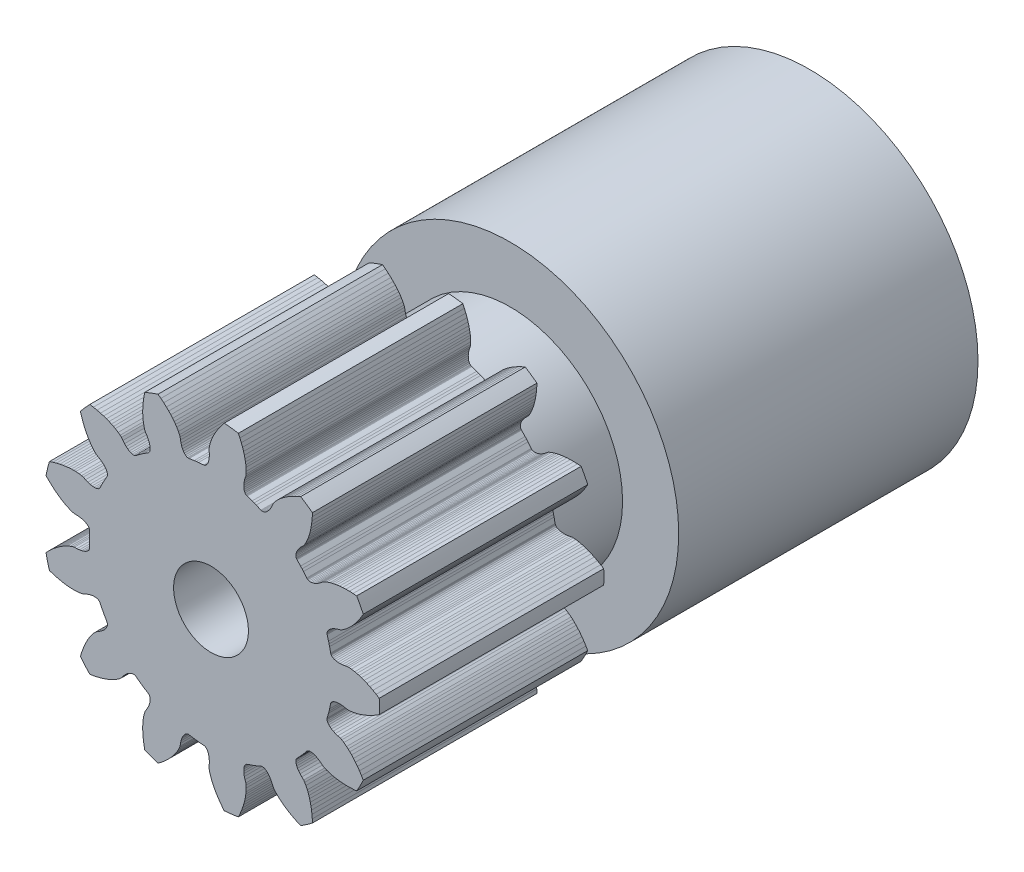
SolidWorks part; units mm, degrees
ref_plane "Front Plane" through (0, 0, 0) normal (0, 0, 1) x (1, 0, 0)
ref_plane "Top Plane" through (0, 0, 0) normal (0, 1, 0) x (1, 0, 0)
ref_plane "Right Plane" through (0, 0, 0) normal (1, 0, 0) x (0, 0, -1)
sketch "Model" plane through (0, 0, 0) normal (0, 0, 1) x (1, 0, 0)
  line L0 (4.021, 1.8382) -> (3.9675, 1.7546)
  line L1 (3.9675, 1.7546) -> (3.9132, 1.6769)
  line L2 (3.9132, 1.6769) -> (3.8601, 1.6075)
  line L3 (3.8601, 1.6075) -> (3.8089, 1.546)
  line L4 (3.8089, 1.546) -> (3.7579, 1.4897)
  line L5 (3.7579, 1.4897) -> (3.7105, 1.4416)
  line L6 (3.7105, 1.4416) -> (3.6651, 1.3992)
  line L7 (3.6651, 1.3992) -> (3.6228, 1.3629)
  line L8 (3.6228, 1.3629) -> (3.5504, 1.3082)
  line L9 (3.5504, 1.3082) -> (3.4948, 1.2729)
  line L10 (3.4948, 1.2729) -> (3.4534, 1.2516)
  line L11 (3.4534, 1.2516) -> (3.3881, 1.2342)
  line L12 (3.3881, 1.2342) -> (3.3241, 1.2119)
  line L13 (3.3241, 1.2119) -> (3.2681, 1.1867)
  line L14 (3.2681, 1.1867) -> (3.2199, 1.1592)
  line L15 (3.2199, 1.1592) -> (3.1798, 1.13)
  line L16 (3.1798, 1.13) -> (3.1477, 1.0998)
  line L17 (3.1477, 1.0998) -> (3.1237, 1.0692)
  line L18 (3.1237, 1.0692) -> (3.1078, 1.0388)
  line L19 (3.1078, 1.0388) -> (3.0998, 1.0092)
  line L20 (3.0998, 1.0092) -> (3.0988, 0.9949)
  line L21 (3.0988, 0.9949) -> (3.0997, 0.9811)
  line L22 (3.0997, 0.9811) -> (3.1026, 0.9677)
  line L23 (3.1026, 0.9677) -> (3.1411, 0.8342)
  line L24 (3.1411, 0.8342) -> (3.1556, 0.7778)
  line L25 (3.1556, 0.7778) -> (3.169, 0.7211)
  line L26 (3.169, 0.7211) -> (3.1969, 0.585)
  line L27 (3.1969, 0.585) -> (3.2006, 0.5718)
  line L28 (3.2006, 0.5718) -> (3.2062, 0.5591)
  line L29 (3.2062, 0.5591) -> (3.2138, 0.5469)
  line L30 (3.2138, 0.5469) -> (3.2346, 0.5244)
  line L31 (3.2346, 0.5244) -> (3.2628, 0.5049)
  line L32 (3.2628, 0.5049) -> (3.2983, 0.489)
  line L33 (3.2983, 0.489) -> (3.3407, 0.4771)
  line L34 (3.3407, 0.4771) -> (3.3898, 0.4699)
  line L35 (3.3898, 0.4699) -> (3.4452, 0.468)
  line L36 (3.4452, 0.468) -> (3.5066, 0.4717)
  line L37 (3.5066, 0.4717) -> (3.5735, 0.4817)
  line L38 (3.5735, 0.4817) -> (3.6395, 0.4967)
  line L39 (3.6395, 0.4967) -> (3.686, 0.497)
  line L40 (3.686, 0.497) -> (3.7517, 0.4916)
  line L41 (3.7517, 0.4916) -> (3.8412, 0.4768)
  line L42 (3.8412, 0.4768) -> (3.8955, 0.4643)
  line L43 (3.8955, 0.4643) -> (3.9555, 0.4479)
  line L44 (3.9555, 0.4479) -> (4.0198, 0.4273)
  line L45 (4.0198, 0.4273) -> (4.0911, 0.4012)
  line L46 (4.0911, 0.4012) -> (4.165, 0.3705)
  line L47 (4.165, 0.3705) -> (4.2442, 0.3337)
  line L48 (4.2442, 0.3337) -> (4.3284, 0.2902)
  line L49 (4.3284, 0.2902) -> (4.4146, 0.241)
  line L50 (4.4146, 0.241) -> (4.496, 0.1901)
  line L51 (4.496, -0.1901) -> (4.4146, -0.241)
  line L52 (4.4146, -0.241) -> (4.3284, -0.2902)
  line L53 (4.3284, -0.2902) -> (4.2442, -0.3337)
  line L54 (4.2442, -0.3337) -> (4.165, -0.3705)
  line L55 (4.165, -0.3705) -> (4.0911, -0.4012)
  line L56 (4.0911, -0.4012) -> (4.0198, -0.4273)
  line L57 (4.0198, -0.4273) -> (3.9555, -0.4479)
  line L58 (3.9555, -0.4479) -> (3.8955, -0.4643)
  line L59 (3.8955, -0.4643) -> (3.8412, -0.4768)
  line L60 (3.8412, -0.4768) -> (3.7517, -0.4916)
  line L61 (3.7517, -0.4916) -> (3.686, -0.497)
  line L62 (3.686, -0.497) -> (3.6395, -0.4967)
  line L63 (3.6395, -0.4967) -> (3.5735, -0.4817)
  line L64 (3.5735, -0.4817) -> (3.5066, -0.4717)
  line L65 (3.5066, -0.4717) -> (3.4452, -0.468)
  line L66 (3.4452, -0.468) -> (3.3898, -0.4699)
  line L67 (3.3898, -0.4699) -> (3.3407, -0.4771)
  line L68 (3.3407, -0.4771) -> (3.2983, -0.489)
  line L69 (3.2983, -0.489) -> (3.2628, -0.5049)
  line L70 (3.2628, -0.5049) -> (3.2346, -0.5244)
  line L71 (3.2346, -0.5244) -> (3.2138, -0.5469)
  line L72 (3.2138, -0.5469) -> (3.2062, -0.5591)
  line L73 (3.2062, -0.5591) -> (3.2006, -0.5718)
  line L74 (3.2006, -0.5718) -> (3.1969, -0.585)
  line L75 (3.1969, -0.585) -> (3.169, -0.7211)
  line L76 (3.169, -0.7211) -> (3.1556, -0.7778)
  line L77 (3.1556, -0.7778) -> (3.1411, -0.8342)
  line L78 (3.1411, -0.8342) -> (3.1026, -0.9677)
  line L79 (3.1026, -0.9677) -> (3.0997, -0.9811)
  line L80 (3.0997, -0.9811) -> (3.0988, -0.9949)
  line L81 (3.0988, -0.9949) -> (3.0998, -1.0092)
  line L82 (3.0998, -1.0092) -> (3.1078, -1.0388)
  line L83 (3.1078, -1.0388) -> (3.1237, -1.0692)
  line L84 (3.1237, -1.0692) -> (3.1477, -1.0998)
  line L85 (3.1477, -1.0998) -> (3.1798, -1.13)
  line L86 (3.1798, -1.13) -> (3.2199, -1.1592)
  line L87 (3.2199, -1.1592) -> (3.2681, -1.1867)
  line L88 (3.2681, -1.1867) -> (3.3241, -1.2119)
  line L89 (3.3241, -1.2119) -> (3.3881, -1.2342)
  line L90 (3.3881, -1.2342) -> (3.4534, -1.2516)
  line L91 (3.4534, -1.2516) -> (3.4948, -1.2729)
  line L92 (3.4948, -1.2729) -> (3.5504, -1.3082)
  line L93 (3.5504, -1.3082) -> (3.6228, -1.3629)
  line L94 (3.6228, -1.3629) -> (3.6651, -1.3992)
  line L95 (3.6651, -1.3992) -> (3.7105, -1.4416)
  line L96 (3.7105, -1.4416) -> (3.7579, -1.4897)
  line L97 (3.7579, -1.4897) -> (3.8089, -1.546)
  line L98 (3.8089, -1.546) -> (3.8601, -1.6075)
  line L99 (3.8601, -1.6075) -> (3.9132, -1.6769)
  line L100 (3.9132, -1.6769) -> (3.9675, -1.7546)
  line L101 (3.9675, -1.7546) -> (4.021, -1.8382)
  line L102 (4.021, -1.8382) -> (4.0693, -1.921)
  line L103 (3.8926, -2.2577) -> (3.7969, -2.265)
  line L104 (3.7969, -2.265) -> (3.6978, -2.2685)
  line L105 (3.6978, -2.2685) -> (3.603, -2.2679)
  line L106 (3.603, -2.2679) -> (3.5158, -2.2636)
  line L107 (3.5158, -2.2636) -> (3.4361, -2.2564)
  line L108 (3.4361, -2.2564) -> (3.3608, -2.2464)
  line L109 (3.3608, -2.2464) -> (3.2943, -2.2348)
  line L110 (3.2943, -2.2348) -> (3.2335, -2.2214)
  line L111 (3.2335, -2.2214) -> (3.1796, -2.2072)
  line L112 (3.1796, -2.2072) -> (3.0935, -2.1788)
  line L113 (3.0935, -2.1788) -> (3.0328, -2.1531)
  line L114 (3.0328, -2.1531) -> (2.9918, -2.1311)
  line L115 (2.9918, -2.1311) -> (2.9404, -2.0872)
  line L116 (2.9404, -2.0872) -> (2.8857, -2.0473)
  line L117 (2.8857, -2.0473) -> (2.8331, -2.0154)
  line L118 (2.8331, -2.0154) -> (2.7831, -1.9914)
  line L119 (2.7831, -1.9914) -> (2.7363, -1.975)
  line L120 (2.7363, -1.975) -> (2.6933, -1.9657)
  line L121 (2.6933, -1.9657) -> (2.6544, -1.9634)
  line L122 (2.6544, -1.9634) -> (2.6204, -1.9676)
  line L123 (2.6204, -1.9676) -> (2.5915, -1.9778)
  line L124 (2.5915, -1.9778) -> (2.5791, -1.9851)
  line L125 (2.5791, -1.9851) -> (2.5683, -1.9937)
  line L126 (2.5683, -1.9937) -> (2.5589, -2.0037)
  line L127 (2.5589, -2.0037) -> (2.4709, -2.1112)
  line L128 (2.4709, -2.1112) -> (2.4327, -2.1551)
  line L129 (2.4327, -2.1551) -> (2.3937, -2.1984)
  line L130 (2.3937, -2.1984) -> (2.2975, -2.2987)
  line L131 (2.2975, -2.2987) -> (2.2888, -2.3092)
  line L132 (2.2888, -2.3092) -> (2.2815, -2.3211)
  line L133 (2.2815, -2.3211) -> (2.2758, -2.3342)
  line L134 (2.2758, -2.3342) -> (2.2691, -2.3641)
  line L135 (2.2691, -2.3641) -> (2.269, -2.3984)
  line L136 (2.269, -2.3984) -> (2.276, -2.4367)
  line L137 (2.276, -2.4367) -> (2.2904, -2.4783)
  line L138 (2.2904, -2.4783) -> (2.3124, -2.5228)
  line L139 (2.3124, -2.5228) -> (2.3422, -2.5695)
  line L140 (2.3422, -2.5695) -> (2.3802, -2.6179)
  line L141 (2.3802, -2.6179) -> (2.4264, -2.6673)
  line L142 (2.4264, -2.6673) -> (2.4762, -2.7131)
  line L143 (2.4762, -2.7131) -> (2.5029, -2.7512)
  line L144 (2.5029, -2.7512) -> (2.5358, -2.8083)
  line L145 (2.5358, -2.8083) -> (2.5744, -2.8904)
  line L146 (2.5744, -2.8904) -> (2.595, -2.9422)
  line L147 (2.595, -2.9422) -> (2.6155, -3.0009)
  line L148 (2.6155, -3.0009) -> (2.6352, -3.0655)
  line L149 (2.6352, -3.0655) -> (2.6542, -3.139)
  line L150 (2.6542, -3.139) -> (2.6709, -3.2173)
  line L151 (2.6709, -3.2173) -> (2.6856, -3.3034)
  line L152 (2.6856, -3.3034) -> (2.6977, -3.3974)
  line L153 (2.6977, -3.3974) -> (2.7061, -3.4962)
  line L154 (2.7061, -3.4962) -> (2.7105, -3.5921)
  line L155 (2.3975, -3.8081) -> (2.3094, -3.7701)
  line L156 (2.3094, -3.7701) -> (2.22, -3.7271)
  line L157 (2.22, -3.7271) -> (2.1364, -3.6825)
  line L158 (2.1364, -3.6825) -> (2.0611, -3.6382)
  line L159 (2.0611, -3.6382) -> (1.9939, -3.5948)
  line L160 (1.9939, -3.5948) -> (1.9318, -3.5509)
  line L161 (1.9318, -3.5509) -> (1.8784, -3.5097)
  line L162 (1.8784, -3.5097) -> (1.8308, -3.4697)
  line L163 (1.8308, -3.4697) -> (1.7897, -3.4321)
  line L164 (1.7897, -3.4321) -> (1.7266, -3.3668)
  line L165 (1.7266, -3.3668) -> (1.6848, -3.3159)
  line L166 (1.6848, -3.3159) -> (1.6587, -3.2774)
  line L167 (1.6587, -3.2774) -> (1.6336, -3.2146)
  line L168 (1.6336, -3.2146) -> (1.6037, -3.1538)
  line L169 (1.6037, -3.1538) -> (1.572, -3.1012)
  line L170 (1.572, -3.1012) -> (1.5389, -3.0567)
  line L171 (1.5389, -3.0567) -> (1.5051, -3.0204)
  line L172 (1.5051, -3.0204) -> (1.4712, -2.9922)
  line L173 (1.4712, -2.9922) -> (1.4379, -2.9721)
  line L174 (1.4379, -2.9721) -> (1.4058, -2.9599)
  line L175 (1.4058, -2.9599) -> (1.3755, -2.9556)
  line L176 (1.3755, -2.9556) -> (1.3612, -2.9563)
  line L177 (1.3612, -2.9563) -> (1.3476, -2.9589)
  line L178 (1.3476, -2.9589) -> (1.3346, -2.9633)
  line L179 (1.3346, -2.9633) -> (1.2067, -3.0177)
  line L180 (1.2067, -3.0177) -> (1.1525, -3.0388)
  line L181 (1.1525, -3.0388) -> (1.0978, -3.059)
  line L182 (1.0978, -3.059) -> (0.9661, -3.1031)
  line L183 (0.9661, -3.1031) -> (0.9534, -3.1084)
  line L184 (0.9534, -3.1084) -> (0.9415, -3.1155)
  line L185 (0.9415, -3.1155) -> (0.9303, -3.1244)
  line L186 (0.9303, -3.1244) -> (0.9105, -3.1478)
  line L187 (0.9105, -3.1478) -> (0.8945, -3.1782)
  line L188 (0.8945, -3.1782) -> (0.883, -3.2153)
  line L189 (0.883, -3.2153) -> (0.8763, -3.2588)
  line L190 (0.8763, -3.2588) -> (0.8751, -3.3084)
  line L191 (0.8751, -3.3084) -> (0.8798, -3.3637)
  line L192 (0.8798, -3.3637) -> (0.891, -3.4242)
  line L193 (0.891, -3.4242) -> (0.9089, -3.4894)
  line L194 (0.9089, -3.4894) -> (0.9317, -3.5531)
  line L195 (0.9317, -3.5531) -> (0.9377, -3.5992)
  line L196 (0.9377, -3.5992) -> (0.9403, -3.665)
  line L197 (0.9403, -3.665) -> (0.9363, -3.7557)
  line L198 (0.9363, -3.7557) -> (0.9305, -3.8111)
  line L199 (0.9305, -3.8111) -> (0.9214, -3.8727)
  line L200 (0.9214, -3.8727) -> (0.9087, -3.939)
  line L201 (0.9087, -3.939) -> (0.8914, -4.0129)
  line L202 (0.8914, -4.0129) -> (0.8698, -4.09)
  line L203 (0.8698, -4.09) -> (0.8429, -4.1731)
  line L204 (0.8429, -4.1731) -> (0.8098, -4.2619)
  line L205 (0.8098, -4.2619) -> (0.7714, -4.3534)
  line L206 (0.7714, -4.3534) -> (0.7307, -4.4403)
  line L207 (0.3532, -4.4861) -> (0.2929, -4.4115)
  line L208 (0.2929, -4.4115) -> (0.2336, -4.3319)
  line L209 (0.2336, -4.3319) -> (0.1803, -4.2535)
  line L210 (0.1803, -4.2535) -> (0.1342, -4.1793)
  line L211 (0.1342, -4.1793) -> (0.0949, -4.1096)
  line L212 (0.0949, -4.1096) -> (0.0603, -4.042)
  line L213 (0.0603, -4.042) -> (0.0322, -3.9806)
  line L214 (0.0322, -3.9806) -> (0.0086, -3.9231)
  line L215 (0.0086, -3.9231) -> (-0.0103, -3.8706)
  line L216 (-0.0103, -3.8706) -> (-0.0358, -3.7836)
  line L217 (-0.0358, -3.7836) -> (-0.0491, -3.719)
  line L218 (-0.0491, -3.719) -> (-0.0544, -3.6728)
  line L219 (-0.0544, -3.6728) -> (-0.0474, -3.6056)
  line L220 (-0.0474, -3.6056) -> (-0.0456, -3.5379)
  line L221 (-0.0456, -3.5379) -> (-0.0493, -3.4765)
  line L222 (-0.0493, -3.4765) -> (-0.0579, -3.4217)
  line L223 (-0.0579, -3.4217) -> (-0.071, -3.3739)
  line L224 (-0.071, -3.3739) -> (-0.0878, -3.3332)
  line L225 (-0.0878, -3.3332) -> (-0.108, -3.2999)
  line L226 (-0.108, -3.2999) -> (-0.1307, -3.2742)
  line L227 (-0.1307, -3.2742) -> (-0.1556, -3.2563)
  line L228 (-0.1556, -3.2563) -> (-0.1686, -3.2503)
  line L229 (-0.1686, -3.2503) -> (-0.1819, -3.2462)
  line L230 (-0.1819, -3.2462) -> (-0.1954, -3.2441)
  line L231 (-0.1954, -3.2441) -> (-0.3339, -3.2328)
  line L232 (-0.3339, -3.2328) -> (-0.3917, -3.2263)
  line L233 (-0.3917, -3.2263) -> (-0.4495, -3.2188)
  line L234 (-0.4495, -3.2188) -> (-0.5867, -3.1966)
  line L235 (-0.5867, -3.1966) -> (-0.6003, -3.1954)
  line L236 (-0.6003, -3.1954) -> (-0.6142, -3.1962)
  line L237 (-0.6142, -3.1962) -> (-0.6282, -3.1989)
  line L238 (-0.6282, -3.1989) -> (-0.6566, -3.2104)
  line L239 (-0.6566, -3.2104) -> (-0.6849, -3.2298)
  line L240 (-0.6849, -3.2298) -> (-0.7124, -3.2573)
  line L241 (-0.7124, -3.2573) -> (-0.7385, -3.2928)
  line L242 (-0.7385, -3.2928) -> (-0.7626, -3.3361)
  line L243 (-0.7626, -3.3361) -> (-0.7841, -3.3873)
  line L244 (-0.7841, -3.3873) -> (-0.8024, -3.446)
  line L245 (-0.8024, -3.446) -> (-0.8168, -3.5121)
  line L246 (-0.8168, -3.5121) -> (-0.8262, -3.5791)
  line L247 (-0.8262, -3.5791) -> (-0.8423, -3.6227)
  line L248 (-0.8423, -3.6227) -> (-0.8707, -3.6822)
  line L249 (-0.8707, -3.6822) -> (-0.9163, -3.7606)
  line L250 (-0.9163, -3.7606) -> (-0.9472, -3.807)
  line L251 (-0.9472, -3.807) -> (-0.9839, -3.8573)
  line L252 (-0.9839, -3.8573) -> (-1.0259, -3.9101)
  line L253 (-1.0259, -3.9101) -> (-1.0756, -3.9675)
  line L254 (-1.0756, -3.9675) -> (-1.1305, -4.0258)
  line L255 (-1.1305, -4.0258) -> (-1.193, -4.0868)
  line L256 (-1.193, -4.0868) -> (-1.2635, -4.1501)
  line L257 (-1.2635, -4.1501) -> (-1.3401, -4.2132)
  line L258 (-1.3401, -4.2132) -> (-1.4165, -4.2712)
  line L259 (-1.7721, -4.1364) -> (-1.7908, -4.0423)
  line L260 (-1.7908, -4.0423) -> (-1.8062, -3.9442)
  line L261 (-1.8062, -3.9442) -> (-1.817, -3.8501)
  line L262 (-1.817, -3.8501) -> (-1.8234, -3.763)
  line L263 (-1.8234, -3.763) -> (-1.8258, -3.683)
  line L264 (-1.8258, -3.683) -> (-1.825, -3.607)
  line L265 (-1.825, -3.607) -> (-1.8214, -3.5396)
  line L266 (-1.8214, -3.5396) -> (-1.8155, -3.4777)
  line L267 (-1.8155, -3.4777) -> (-1.8079, -3.4225)
  line L268 (-1.8079, -3.4225) -> (-1.79, -3.3335)
  line L269 (-1.79, -3.3335) -> (-1.7718, -3.2702)
  line L270 (-1.7718, -3.2702) -> (-1.755, -3.2268)
  line L271 (-1.755, -3.2268) -> (-1.7176, -3.1705)
  line L272 (-1.7176, -3.1705) -> (-1.6845, -3.1114)
  line L273 (-1.6845, -3.1114) -> (-1.6593, -3.0554)
  line L274 (-1.6593, -3.0554) -> (-1.6414, -3.0029)
  line L275 (-1.6414, -3.0029) -> (-1.6307, -2.9544)
  line L276 (-1.6307, -2.9544) -> (-1.6268, -2.9106)
  line L277 (-1.6268, -2.9106) -> (-1.6291, -2.8717)
  line L278 (-1.6291, -2.8717) -> (-1.6374, -2.8384)
  line L279 (-1.6374, -2.8384) -> (-1.651, -2.811)
  line L280 (-1.651, -2.811) -> (-1.6597, -2.7996)
  line L281 (-1.6597, -2.7996) -> (-1.6696, -2.7899)
  line L282 (-1.6696, -2.7899) -> (-1.6806, -2.7817)
  line L283 (-1.6806, -2.7817) -> (-1.798, -2.7074)
  line L284 (-1.798, -2.7074) -> (-1.8462, -2.6747)
  line L285 (-1.8462, -2.6747) -> (-1.8938, -2.6412)
  line L286 (-1.8938, -2.6412) -> (-2.005, -2.5578)
  line L287 (-2.005, -2.5578) -> (-2.0165, -2.5504)
  line L288 (-2.0165, -2.5504) -> (-2.0291, -2.5446)
  line L289 (-2.0291, -2.5446) -> (-2.0429, -2.5405)
  line L290 (-2.0429, -2.5405) -> (-2.0733, -2.5375)
  line L291 (-2.0733, -2.5375) -> (-2.1074, -2.5416)
  line L292 (-2.1074, -2.5416) -> (-2.1446, -2.5532)
  line L293 (-2.1446, -2.5532) -> (-2.1842, -2.5724)
  line L294 (-2.1842, -2.5724) -> (-2.2257, -2.5996)
  line L295 (-2.2257, -2.5996) -> (-2.2684, -2.6349)
  line L296 (-2.2684, -2.6349) -> (-2.3119, -2.6784)
  line L297 (-2.3119, -2.6784) -> (-2.3554, -2.7302)
  line L298 (-2.3554, -2.7302) -> (-2.3948, -2.7852)
  line L299 (-2.3948, -2.7852) -> (-2.4294, -2.8163)
  line L300 (-2.4294, -2.8163) -> (-2.4821, -2.8558)
  line L301 (-2.4821, -2.8558) -> (-2.559, -2.904)
  line L302 (-2.559, -2.904) -> (-2.6079, -2.9307)
  line L303 (-2.6079, -2.9307) -> (-2.6637, -2.9582)
  line L304 (-2.6637, -2.9582) -> (-2.7255, -2.9854)
  line L305 (-2.7255, -2.9854) -> (-2.7962, -3.0132)
  line L306 (-2.7962, -3.0132) -> (-2.8719, -3.0392)
  line L307 (-2.8719, -3.0392) -> (-2.9556, -3.0642)
  line L308 (-2.9556, -3.0642) -> (-3.0474, -3.0875)
  line L309 (-3.0474, -3.0875) -> (-3.1446, -3.1078)
  line L310 (-3.1446, -3.1078) -> (-3.2392, -3.1237)
  line L311 (-3.4914, -2.8391) -> (-3.4642, -2.747)
  line L312 (-3.4642, -2.747) -> (-3.4323, -2.6531)
  line L313 (-3.4323, -2.6531) -> (-3.3981, -2.5647)
  line L314 (-3.3981, -2.5647) -> (-3.3633, -2.4846)
  line L315 (-3.3633, -2.4846) -> (-3.3283, -2.4126)
  line L316 (-3.3283, -2.4126) -> (-3.2922, -2.3458)
  line L317 (-3.2922, -2.3458) -> (-3.2577, -2.2877)
  line L318 (-3.2577, -2.2877) -> (-3.2237, -2.2357)
  line L319 (-3.2237, -2.2357) -> (-3.1913, -2.1903)
  line L320 (-3.1913, -2.1903) -> (-3.1342, -2.1198)
  line L321 (-3.1342, -2.1198) -> (-3.0886, -2.0722)
  line L322 (-3.0886, -2.0722) -> (-3.0535, -2.0417)
  line L323 (-3.0535, -2.0417) -> (-2.9943, -2.0092)
  line L324 (-2.9943, -2.0092) -> (-2.9375, -1.9722)
  line L325 (-2.9375, -1.9722) -> (-2.8891, -1.9343)
  line L326 (-2.8891, -1.9343) -> (-2.8489, -1.8961)
  line L327 (-2.8489, -1.8961) -> (-2.8169, -1.8582)
  line L328 (-2.8169, -1.8582) -> (-2.793, -1.8212)
  line L329 (-2.793, -1.8212) -> (-2.7771, -1.7857)
  line L330 (-2.7771, -1.7857) -> (-2.7689, -1.7524)
  line L331 (-2.7689, -1.7524) -> (-2.7682, -1.7217)
  line L332 (-2.7682, -1.7217) -> (-2.7707, -1.7076)
  line L333 (-2.7707, -1.7076) -> (-2.7749, -1.6944)
  line L334 (-2.7749, -1.6944) -> (-2.7808, -1.6821)
  line L335 (-2.7808, -1.6821) -> (-2.8502, -1.5617)
  line L336 (-2.8502, -1.5617) -> (-2.8777, -1.5103)
  line L337 (-2.8777, -1.5103) -> (-2.9043, -1.4586)
  line L338 (-2.9043, -1.4586) -> (-2.964, -1.3331)
  line L339 (-2.964, -1.3331) -> (-2.9708, -1.3212)
  line L340 (-2.9708, -1.3212) -> (-2.9793, -1.3102)
  line L341 (-2.9793, -1.3102) -> (-2.9895, -1.3002)
  line L342 (-2.9895, -1.3002) -> (-3.0151, -1.2833)
  line L343 (-3.0151, -1.2833) -> (-3.0472, -1.2711)
  line L344 (-3.0472, -1.2711) -> (-3.0854, -1.2641)
  line L345 (-3.0854, -1.2641) -> (-3.1294, -1.2627)
  line L346 (-3.1294, -1.2627) -> (-3.1788, -1.2675)
  line L347 (-3.1788, -1.2675) -> (-3.2331, -1.2789)
  line L348 (-3.2331, -1.2789) -> (-3.2918, -1.2972)
  line L349 (-3.2918, -1.2972) -> (-3.3544, -1.3229)
  line L350 (-3.3544, -1.3229) -> (-3.4149, -1.3532)
  line L351 (-3.4149, -1.3532) -> (-3.4599, -1.3647)
  line L352 (-3.4599, -1.3647) -> (-3.525, -1.3752)
  line L353 (-3.525, -1.3752) -> (-3.6155, -1.3822)
  line L354 (-3.6155, -1.3822) -> (-3.6712, -1.3831)
  line L355 (-3.6712, -1.3831) -> (-3.7334, -1.3815)
  line L356 (-3.7334, -1.3815) -> (-3.8007, -1.3769)
  line L357 (-3.8007, -1.3769) -> (-3.8762, -1.3686)
  line L358 (-3.8762, -1.3686) -> (-3.9553, -1.3565)
  line L359 (-3.9553, -1.3565) -> (-4.0411, -1.3397)
  line L360 (-4.0411, -1.3397) -> (-4.1332, -1.3176)
  line L361 (-4.1332, -1.3176) -> (-4.2287, -1.2905)
  line L362 (-4.2287, -1.2905) -> (-4.3198, -1.2606)
  line L363 (-4.4108, -0.8913) -> (-4.344, -0.8225)
  line L364 (-4.344, -0.8225) -> (-4.2721, -0.7541)
  line L365 (-4.2721, -0.7541) -> (-4.2008, -0.6917)
  line L366 (-4.2008, -0.6917) -> (-4.1327, -0.637)
  line L367 (-4.1327, -0.637) -> (-4.0682, -0.5896)
  line L368 (-4.0682, -0.5896) -> (-4.0052, -0.5471)
  line L369 (-4.0052, -0.5471) -> (-3.9477, -0.5118)
  line L370 (-3.9477, -0.5118) -> (-3.8934, -0.4814)
  line L371 (-3.8934, -0.4814) -> (-3.8437, -0.4563)
  line L372 (-3.8437, -0.4563) -> (-3.7603, -0.4205)
  line L373 (-3.7603, -0.4205) -> (-3.6978, -0.3995)
  line L374 (-3.6978, -0.3995) -> (-3.6526, -0.3887)
  line L375 (-3.6526, -0.3887) -> (-3.585, -0.3875)
  line L376 (-3.585, -0.3875) -> (-3.5176, -0.3812)
  line L377 (-3.5176, -0.3812) -> (-3.4571, -0.3701)
  line L378 (-3.4571, -0.3701) -> (-3.4037, -0.3549)
  line L379 (-3.4037, -0.3549) -> (-3.3578, -0.3362)
  line L380 (-3.3578, -0.3362) -> (-3.3195, -0.3146)
  line L381 (-3.3195, -0.3146) -> (-3.2888, -0.2906)
  line L382 (-3.2888, -0.2906) -> (-3.2661, -0.2649)
  line L383 (-3.2661, -0.2649) -> (-3.2513, -0.2381)
  line L384 (-3.2513, -0.2381) -> (-3.2469, -0.2244)
  line L385 (-3.2469, -0.2244) -> (-3.2445, -0.2107)
  line L386 (-3.2445, -0.2107) -> (-3.244, -0.1971)
  line L387 (-3.244, -0.1971) -> (-3.2495, -0.0582)
  line L388 (-3.2495, -0.0582) -> (-3.25, 0)
  line L389 (-3.25, 0) -> (-3.2495, 0.0582)
  line L390 (-3.2495, 0.0582) -> (-3.244, 0.1971)
  line L391 (-3.244, 0.1971) -> (-3.2445, 0.2108)
  line L392 (-3.2445, 0.2108) -> (-3.2469, 0.2244)
  line L393 (-3.2469, 0.2244) -> (-3.2513, 0.2381)
  line L394 (-3.2513, 0.2381) -> (-3.2661, 0.2649)
  line L395 (-3.2661, 0.2649) -> (-3.2888, 0.2906)
  line L396 (-3.2888, 0.2906) -> (-3.3195, 0.3146)
  line L397 (-3.3195, 0.3146) -> (-3.3578, 0.3362)
  line L398 (-3.3578, 0.3362) -> (-3.4037, 0.3549)
  line L399 (-3.4037, 0.3549) -> (-3.4571, 0.3701)
  line L400 (-3.4571, 0.3701) -> (-3.5176, 0.3812)
  line L401 (-3.5176, 0.3812) -> (-3.585, 0.3875)
  line L402 (-3.585, 0.3875) -> (-3.6526, 0.3887)
  line L403 (-3.6526, 0.3887) -> (-3.6978, 0.3995)
  line L404 (-3.6978, 0.3995) -> (-3.7603, 0.4205)
  line L405 (-3.7603, 0.4205) -> (-3.8437, 0.4563)
  line L406 (-3.8437, 0.4563) -> (-3.8934, 0.4815)
  line L407 (-3.8934, 0.4815) -> (-3.9477, 0.5118)
  line L408 (-3.9477, 0.5118) -> (-4.0052, 0.5471)
  line L409 (-4.0052, 0.5471) -> (-4.0682, 0.5896)
  line L410 (-4.0682, 0.5896) -> (-4.1327, 0.637)
  line L411 (-4.1327, 0.637) -> (-4.2008, 0.6917)
  line L412 (-4.2008, 0.6917) -> (-4.2721, 0.7541)
  line L413 (-4.2721, 0.7541) -> (-4.344, 0.8225)
  line L414 (-4.344, 0.8225) -> (-4.4109, 0.8913)
  line L415 (-4.3198, 1.2606) -> (-4.2287, 1.2905)
  line L416 (-4.2287, 1.2905) -> (-4.1332, 1.3176)
  line L417 (-4.1332, 1.3176) -> (-4.0411, 1.3397)
  line L418 (-4.0411, 1.3397) -> (-3.9553, 1.3565)
  line L419 (-3.9553, 1.3565) -> (-3.8762, 1.3686)
  line L420 (-3.8762, 1.3686) -> (-3.8007, 1.3769)
  line L421 (-3.8007, 1.3769) -> (-3.7334, 1.3815)
  line L422 (-3.7334, 1.3815) -> (-3.6712, 1.3831)
  line L423 (-3.6712, 1.3831) -> (-3.6155, 1.3822)
  line L424 (-3.6155, 1.3822) -> (-3.525, 1.3752)
  line L425 (-3.525, 1.3752) -> (-3.4599, 1.3647)
  line L426 (-3.4599, 1.3647) -> (-3.4149, 1.3532)
  line L427 (-3.4149, 1.3532) -> (-3.3544, 1.3229)
  line L428 (-3.3544, 1.3229) -> (-3.2918, 1.2972)
  line L429 (-3.2918, 1.2972) -> (-3.2331, 1.2789)
  line L430 (-3.2331, 1.2789) -> (-3.1788, 1.2675)
  line L431 (-3.1788, 1.2675) -> (-3.1294, 1.2627)
  line L432 (-3.1294, 1.2627) -> (-3.0854, 1.2641)
  line L433 (-3.0854, 1.2641) -> (-3.0472, 1.2711)
  line L434 (-3.0472, 1.2711) -> (-3.0151, 1.2833)
  line L435 (-3.0151, 1.2833) -> (-2.9895, 1.3002)
  line L436 (-2.9895, 1.3002) -> (-2.9793, 1.3102)
  line L437 (-2.9793, 1.3102) -> (-2.9708, 1.3212)
  line L438 (-2.9708, 1.3212) -> (-2.964, 1.3331)
  line L439 (-2.964, 1.3331) -> (-2.9043, 1.4586)
  line L440 (-2.9043, 1.4586) -> (-2.8777, 1.5104)
  line L441 (-2.8777, 1.5104) -> (-2.8502, 1.5617)
  line L442 (-2.8502, 1.5617) -> (-2.7808, 1.6821)
  line L443 (-2.7808, 1.6821) -> (-2.7749, 1.6944)
  line L444 (-2.7749, 1.6944) -> (-2.7707, 1.7076)
  line L445 (-2.7707, 1.7076) -> (-2.7682, 1.7217)
  line L446 (-2.7682, 1.7217) -> (-2.7689, 1.7524)
  line L447 (-2.7689, 1.7524) -> (-2.7771, 1.7857)
  line L448 (-2.7771, 1.7857) -> (-2.793, 1.8212)
  line L449 (-2.793, 1.8212) -> (-2.8169, 1.8582)
  line L450 (-2.8169, 1.8582) -> (-2.8489, 1.8961)
  line L451 (-2.8489, 1.8961) -> (-2.8891, 1.9343)
  line L452 (-2.8891, 1.9343) -> (-2.9375, 1.9722)
  line L453 (-2.9375, 1.9722) -> (-2.9943, 2.0092)
  line L454 (-2.9943, 2.0092) -> (-3.0535, 2.0417)
  line L455 (-3.0535, 2.0417) -> (-3.0886, 2.0722)
  line L456 (-3.0886, 2.0722) -> (-3.1342, 2.1198)
  line L457 (-3.1342, 2.1198) -> (-3.1913, 2.1903)
  line L458 (-3.1913, 2.1903) -> (-3.2237, 2.2357)
  line L459 (-3.2237, 2.2357) -> (-3.2577, 2.2877)
  line L460 (-3.2577, 2.2877) -> (-3.2922, 2.3458)
  line L461 (-3.2922, 2.3458) -> (-3.3283, 2.4126)
  line L462 (-3.3283, 2.4126) -> (-3.3633, 2.4846)
  line L463 (-3.3633, 2.4846) -> (-3.3981, 2.5647)
  line L464 (-3.3981, 2.5647) -> (-3.4323, 2.6531)
  line L465 (-3.4323, 2.6531) -> (-3.4642, 2.747)
  line L466 (-3.4642, 2.747) -> (-3.4914, 2.8391)
  line L467 (-3.2392, 3.1237) -> (-3.1446, 3.1078)
  line L468 (-3.1446, 3.1078) -> (-3.0474, 3.0875)
  line L469 (-3.0474, 3.0875) -> (-2.9556, 3.0642)
  line L470 (-2.9556, 3.0642) -> (-2.8719, 3.0392)
  line L471 (-2.8719, 3.0392) -> (-2.7962, 3.0132)
  line L472 (-2.7962, 3.0132) -> (-2.7255, 2.9854)
  line L473 (-2.7255, 2.9854) -> (-2.6637, 2.9582)
  line L474 (-2.6637, 2.9582) -> (-2.6079, 2.9307)
  line L475 (-2.6079, 2.9307) -> (-2.559, 2.904)
  line L476 (-2.559, 2.904) -> (-2.4821, 2.8558)
  line L477 (-2.4821, 2.8558) -> (-2.4294, 2.8163)
  line L478 (-2.4294, 2.8163) -> (-2.3948, 2.7852)
  line L479 (-2.3948, 2.7852) -> (-2.3554, 2.7302)
  line L480 (-2.3554, 2.7302) -> (-2.3119, 2.6784)
  line L481 (-2.3119, 2.6784) -> (-2.2684, 2.6349)
  line L482 (-2.2684, 2.6349) -> (-2.2257, 2.5996)
  line L483 (-2.2257, 2.5996) -> (-2.1842, 2.5724)
  line L484 (-2.1842, 2.5724) -> (-2.1446, 2.5532)
  line L485 (-2.1446, 2.5532) -> (-2.1074, 2.5416)
  line L486 (-2.1074, 2.5416) -> (-2.0733, 2.5375)
  line L487 (-2.0733, 2.5375) -> (-2.0429, 2.5405)
  line L488 (-2.0429, 2.5405) -> (-2.0291, 2.5446)
  line L489 (-2.0291, 2.5446) -> (-2.0165, 2.5504)
  line L490 (-2.0165, 2.5504) -> (-2.005, 2.5578)
  line L491 (-2.005, 2.5578) -> (-1.8938, 2.6412)
  line L492 (-1.8938, 2.6412) -> (-1.8462, 2.6747)
  line L493 (-1.8462, 2.6747) -> (-1.798, 2.7074)
  line L494 (-1.798, 2.7074) -> (-1.6806, 2.7817)
  line L495 (-1.6806, 2.7817) -> (-1.6696, 2.7899)
  line L496 (-1.6696, 2.7899) -> (-1.6597, 2.7996)
  line L497 (-1.6597, 2.7996) -> (-1.651, 2.811)
  line L498 (-1.651, 2.811) -> (-1.6374, 2.8384)
  line L499 (-1.6374, 2.8384) -> (-1.6291, 2.8717)
  line L500 (-1.6291, 2.8717) -> (-1.6268, 2.9106)
  line L501 (-1.6268, 2.9106) -> (-1.6307, 2.9544)
  line L502 (-1.6307, 2.9544) -> (-1.6414, 3.0029)
  line L503 (-1.6414, 3.0029) -> (-1.6593, 3.0554)
  line L504 (-1.6593, 3.0554) -> (-1.6845, 3.1114)
  line L505 (-1.6845, 3.1114) -> (-1.7176, 3.1705)
  line L506 (-1.7176, 3.1705) -> (-1.755, 3.2268)
  line L507 (-1.755, 3.2268) -> (-1.7718, 3.2702)
  line L508 (-1.7718, 3.2702) -> (-1.79, 3.3335)
  line L509 (-1.79, 3.3335) -> (-1.8079, 3.4225)
  line L510 (-1.8079, 3.4225) -> (-1.8155, 3.4777)
  line L511 (-1.8155, 3.4777) -> (-1.8214, 3.5396)
  line L512 (-1.8214, 3.5396) -> (-1.825, 3.607)
  line L513 (-1.825, 3.607) -> (-1.8258, 3.683)
  line L514 (-1.8258, 3.683) -> (-1.8234, 3.763)
  line L515 (-1.8234, 3.763) -> (-1.817, 3.8501)
  line L516 (-1.817, 3.8501) -> (-1.8062, 3.9442)
  line L517 (-1.8062, 3.9442) -> (-1.7908, 4.0423)
  line L518 (-1.7908, 4.0423) -> (-1.7721, 4.1364)
  line L519 (-1.4165, 4.2712) -> (-1.3401, 4.2132)
  line L520 (-1.3401, 4.2132) -> (-1.2635, 4.1501)
  line L521 (-1.2635, 4.1501) -> (-1.193, 4.0868)
  line L522 (-1.193, 4.0868) -> (-1.1305, 4.0258)
  line L523 (-1.1305, 4.0258) -> (-1.0756, 3.9675)
  line L524 (-1.0756, 3.9675) -> (-1.0259, 3.9101)
  line L525 (-1.0259, 3.9101) -> (-0.9839, 3.8573)
  line L526 (-0.9839, 3.8573) -> (-0.9472, 3.807)
  line L527 (-0.9472, 3.807) -> (-0.9163, 3.7606)
  line L528 (-0.9163, 3.7606) -> (-0.8707, 3.6822)
  line L529 (-0.8707, 3.6822) -> (-0.8423, 3.6227)
  line L530 (-0.8423, 3.6227) -> (-0.8262, 3.5791)
  line L531 (-0.8262, 3.5791) -> (-0.8168, 3.5121)
  line L532 (-0.8168, 3.5121) -> (-0.8024, 3.446)
  line L533 (-0.8024, 3.446) -> (-0.7841, 3.3873)
  line L534 (-0.7841, 3.3873) -> (-0.7626, 3.3361)
  line L535 (-0.7626, 3.3361) -> (-0.7385, 3.2928)
  line L536 (-0.7385, 3.2928) -> (-0.7124, 3.2573)
  line L537 (-0.7124, 3.2573) -> (-0.6849, 3.2298)
  line L538 (-0.6849, 3.2298) -> (-0.6566, 3.2104)
  line L539 (-0.6566, 3.2104) -> (-0.6282, 3.1989)
  line L540 (-0.6282, 3.1989) -> (-0.6142, 3.1962)
  line L541 (-0.6142, 3.1962) -> (-0.6003, 3.1954)
  line L542 (-0.6003, 3.1954) -> (-0.5867, 3.1966)
  line L543 (-0.5867, 3.1966) -> (-0.4495, 3.2188)
  line L544 (-0.4495, 3.2188) -> (-0.3917, 3.2263)
  line L545 (-0.3917, 3.2263) -> (-0.3339, 3.2328)
  line L546 (-0.3339, 3.2328) -> (-0.1954, 3.2441)
  line L547 (-0.1954, 3.2441) -> (-0.1819, 3.2462)
  line L548 (-0.1819, 3.2462) -> (-0.1686, 3.2503)
  line L549 (-0.1686, 3.2503) -> (-0.1556, 3.2563)
  line L550 (-0.1556, 3.2563) -> (-0.1307, 3.2742)
  line L551 (-0.1307, 3.2742) -> (-0.108, 3.2999)
  line L552 (-0.108, 3.2999) -> (-0.0878, 3.3332)
  line L553 (-0.0878, 3.3332) -> (-0.071, 3.3739)
  line L554 (-0.071, 3.3739) -> (-0.0579, 3.4217)
  line L555 (-0.0579, 3.4217) -> (-0.0493, 3.4765)
  line L556 (-0.0493, 3.4765) -> (-0.0456, 3.5379)
  line L557 (-0.0456, 3.5379) -> (-0.0474, 3.6056)
  line L558 (-0.0474, 3.6056) -> (-0.0544, 3.6728)
  line L559 (-0.0544, 3.6728) -> (-0.0491, 3.719)
  line L560 (-0.0491, 3.719) -> (-0.0358, 3.7836)
  line L561 (-0.0358, 3.7836) -> (-0.0103, 3.8706)
  line L562 (-0.0103, 3.8706) -> (0.0086, 3.9231)
  line L563 (0.0086, 3.9231) -> (0.0322, 3.9806)
  line L564 (0.0322, 3.9806) -> (0.0603, 4.042)
  line L565 (0.0603, 4.042) -> (0.0949, 4.1096)
  line L566 (0.0949, 4.1096) -> (0.1342, 4.1793)
  line L567 (0.1342, 4.1793) -> (0.1803, 4.2535)
  line L568 (0.1803, 4.2535) -> (0.2336, 4.3319)
  line L569 (0.2336, 4.3319) -> (0.2929, 4.4115)
  line L570 (0.2929, 4.4115) -> (0.3532, 4.4861)
  line L571 (0.7307, 4.4403) -> (0.7714, 4.3534)
  line L572 (0.7714, 4.3534) -> (0.8098, 4.2619)
  line L573 (0.8098, 4.2619) -> (0.8429, 4.1731)
  line L574 (0.8429, 4.1731) -> (0.8698, 4.09)
  line L575 (0.8698, 4.09) -> (0.8914, 4.0129)
  line L576 (0.8914, 4.0129) -> (0.9087, 3.939)
  line L577 (0.9087, 3.939) -> (0.9214, 3.8727)
  line L578 (0.9214, 3.8727) -> (0.9305, 3.8111)
  line L579 (0.9305, 3.8111) -> (0.9363, 3.7557)
  line L580 (0.9363, 3.7557) -> (0.9403, 3.665)
  line L581 (0.9403, 3.665) -> (0.9377, 3.5992)
  line L582 (0.9377, 3.5992) -> (0.9317, 3.5531)
  line L583 (0.9317, 3.5531) -> (0.9089, 3.4894)
  line L584 (0.9089, 3.4894) -> (0.891, 3.4242)
  line L585 (0.891, 3.4242) -> (0.8798, 3.3637)
  line L586 (0.8798, 3.3637) -> (0.8751, 3.3084)
  line L587 (0.8751, 3.3084) -> (0.8763, 3.2588)
  line L588 (0.8763, 3.2588) -> (0.883, 3.2153)
  line L589 (0.883, 3.2153) -> (0.8945, 3.1782)
  line L590 (0.8945, 3.1782) -> (0.9105, 3.1478)
  line L591 (0.9105, 3.1478) -> (0.9303, 3.1244)
  line L592 (0.9303, 3.1244) -> (0.9415, 3.1155)
  line L593 (0.9415, 3.1155) -> (0.9534, 3.1084)
  line L594 (0.9534, 3.1084) -> (0.9661, 3.1031)
  line L595 (0.9661, 3.1031) -> (1.0978, 3.059)
  line L596 (1.0978, 3.059) -> (1.1525, 3.0388)
  line L597 (1.1525, 3.0388) -> (1.2067, 3.0177)
  line L598 (1.2067, 3.0177) -> (1.3346, 2.9633)
  line L599 (1.3346, 2.9633) -> (1.3476, 2.9589)
  line L600 (1.3476, 2.9589) -> (1.3612, 2.9563)
  line L601 (1.3612, 2.9563) -> (1.3755, 2.9556)
  line L602 (1.3755, 2.9556) -> (1.4058, 2.9599)
  line L603 (1.4058, 2.9599) -> (1.4379, 2.9721)
  line L604 (1.4379, 2.9721) -> (1.4712, 2.9922)
  line L605 (1.4712, 2.9922) -> (1.5051, 3.0204)
  line L606 (1.5051, 3.0204) -> (1.5389, 3.0567)
  line L607 (1.5389, 3.0567) -> (1.572, 3.1012)
  line L608 (1.572, 3.1012) -> (1.6037, 3.1538)
  line L609 (1.6037, 3.1538) -> (1.6336, 3.2146)
  line L610 (1.6336, 3.2146) -> (1.6587, 3.2774)
  line L611 (1.6587, 3.2774) -> (1.6848, 3.3159)
  line L612 (1.6848, 3.3159) -> (1.7266, 3.3668)
  line L613 (1.7266, 3.3668) -> (1.7897, 3.4321)
  line L614 (1.7897, 3.4321) -> (1.8308, 3.4697)
  line L615 (1.8308, 3.4697) -> (1.8784, 3.5097)
  line L616 (1.8784, 3.5097) -> (1.9318, 3.5509)
  line L617 (1.9318, 3.5509) -> (1.9939, 3.5948)
  line L618 (1.9939, 3.5948) -> (2.0611, 3.6382)
  line L619 (2.0611, 3.6382) -> (2.1364, 3.6825)
  line L620 (2.1364, 3.6825) -> (2.22, 3.7271)
  line L621 (2.22, 3.7271) -> (2.3094, 3.7701)
  line L622 (2.3094, 3.7701) -> (2.3975, 3.8081)
  line L623 (2.7105, 3.5921) -> (2.7061, 3.4962)
  line L624 (2.7061, 3.4962) -> (2.6977, 3.3974)
  line L625 (2.6977, 3.3974) -> (2.6856, 3.3034)
  line L626 (2.6856, 3.3034) -> (2.6709, 3.2173)
  line L627 (2.6709, 3.2173) -> (2.6542, 3.139)
  line L628 (2.6542, 3.139) -> (2.6352, 3.0655)
  line L629 (2.6352, 3.0655) -> (2.6156, 3.0009)
  line L630 (2.6156, 3.0009) -> (2.595, 2.9422)
  line L631 (2.595, 2.9422) -> (2.5744, 2.8904)
  line L632 (2.5744, 2.8904) -> (2.5358, 2.8083)
  line L633 (2.5358, 2.8083) -> (2.5029, 2.7512)
  line L634 (2.5029, 2.7512) -> (2.4762, 2.7131)
  line L635 (2.4762, 2.7131) -> (2.4264, 2.6673)
  line L636 (2.4264, 2.6673) -> (2.3802, 2.6179)
  line L637 (2.3802, 2.6179) -> (2.3422, 2.5695)
  line L638 (2.3422, 2.5695) -> (2.3124, 2.5228)
  line L639 (2.3124, 2.5228) -> (2.2904, 2.4783)
  line L640 (2.2904, 2.4783) -> (2.276, 2.4367)
  line L641 (2.276, 2.4367) -> (2.269, 2.3984)
  line L642 (2.269, 2.3984) -> (2.2691, 2.3641)
  line L643 (2.2691, 2.3641) -> (2.2758, 2.3342)
  line L644 (2.2758, 2.3342) -> (2.2815, 2.3211)
  line L645 (2.2815, 2.3211) -> (2.2888, 2.3092)
  line L646 (2.2888, 2.3092) -> (2.2975, 2.2987)
  line L647 (2.2975, 2.2987) -> (2.3937, 2.1984)
  line L648 (2.3937, 2.1984) -> (2.4327, 2.1551)
  line L649 (2.4327, 2.1551) -> (2.4709, 2.1112)
  line L650 (2.4709, 2.1112) -> (2.5589, 2.0037)
  line L651 (2.5589, 2.0037) -> (2.5683, 1.9937)
  line L652 (2.5683, 1.9937) -> (2.5791, 1.9851)
  line L653 (2.5791, 1.9851) -> (2.5915, 1.9778)
  line L654 (2.5915, 1.9778) -> (2.6204, 1.9676)
  line L655 (2.6204, 1.9676) -> (2.6544, 1.9634)
  line L656 (2.6544, 1.9634) -> (2.6933, 1.9657)
  line L657 (2.6933, 1.9657) -> (2.7363, 1.975)
  line L658 (2.7363, 1.975) -> (2.7831, 1.9914)
  line L659 (2.7831, 1.9914) -> (2.8331, 2.0154)
  line L660 (2.8331, 2.0154) -> (2.8857, 2.0473)
  line L661 (2.8857, 2.0473) -> (2.9404, 2.0872)
  line L662 (2.9404, 2.0872) -> (2.9918, 2.1311)
  line L663 (2.9918, 2.1311) -> (3.0328, 2.1531)
  line L664 (3.0328, 2.1531) -> (3.0935, 2.1788)
  line L665 (3.0935, 2.1788) -> (3.1796, 2.2073)
  line L666 (3.1796, 2.2073) -> (3.2335, 2.2215)
  line L667 (3.2335, 2.2215) -> (3.2943, 2.2348)
  line L668 (3.2943, 2.2348) -> (3.3608, 2.2464)
  line L669 (3.3608, 2.2464) -> (3.4361, 2.2564)
  line L670 (3.4361, 2.2564) -> (3.5158, 2.2636)
  line L671 (3.5158, 2.2636) -> (3.603, 2.2679)
  line L672 (3.603, 2.2679) -> (3.6978, 2.2685)
  line L673 (3.6978, 2.2685) -> (3.7969, 2.265)
  line L674 (3.7969, 2.265) -> (3.8926, 2.2577)
  line L675 (4.0693, 1.921) -> (4.021, 1.8382)
  arc A0 (3.8926, -2.2577) -> (4.0693, -1.921) centre (0, 0) ccw
  circle A1 centre (0, 0) radius 1
  arc A2 (4.496, -0.1901) -> (4.496, 0.1901) centre (0, 0) ccw
  arc A3 (0.3532, -4.4861) -> (0.7307, -4.4403) centre (0, 0) ccw
  arc A4 (2.3975, -3.8081) -> (2.7105, -3.5921) centre (0, 0) ccw
  arc A5 (-3.4914, -2.8391) -> (-3.2392, -3.1237) centre (0, 0) ccw
  arc A6 (-1.7721, -4.1364) -> (-1.4165, -4.2712) centre (0, 0) ccw
  arc A7 (-4.3198, 1.2606) -> (-4.4109, 0.8913) centre (0, 0) ccw
  arc A8 (-4.4108, -0.8913) -> (-4.3198, -1.2606) centre (0, 0) ccw
  arc A9 (-1.4165, 4.2712) -> (-1.7721, 4.1364) centre (0, 0) ccw
  arc A10 (-3.2392, 3.1237) -> (-3.4914, 2.8391) centre (0, 0) ccw
  arc A12 (0.7307, 4.4403) -> (0.3532, 4.4861) centre (0, 0) ccw
  arc A13 (2.7105, 3.5921) -> (2.3975, 3.8081) centre (0, 0) ccw
  arc A14 (4.0693, 1.921) -> (3.8926, 2.2577) centre (0, 0) ccw
  dimension "D1" = 2
extrude "Boss-Extrude1" add sketch "Model" along normal blind 6
sketch "Sketch2" plane through (0, 0, 0) normal (0, 0, -1) x (-1, 0, 0)
  circle A0 centre (0, 0) radius 3
  dimension "D1" = 6
extrude "Boss-Extrude2" add sketch "Sketch2" along normal blind 3
sketch "Sketch3" plane through (0, 0, -3) normal (0, 0, -1) x (-1, 0, 0)
  circle A0 centre (0, 0) radius 4.5
  circle A1 centre (0, 0) radius 3
  dimension "D1" = 9
  dimension "D2" = 6
extrude "Boss-Extrude3" add sketch "Sketch3" along normal blind 7 and the other way blind 1
